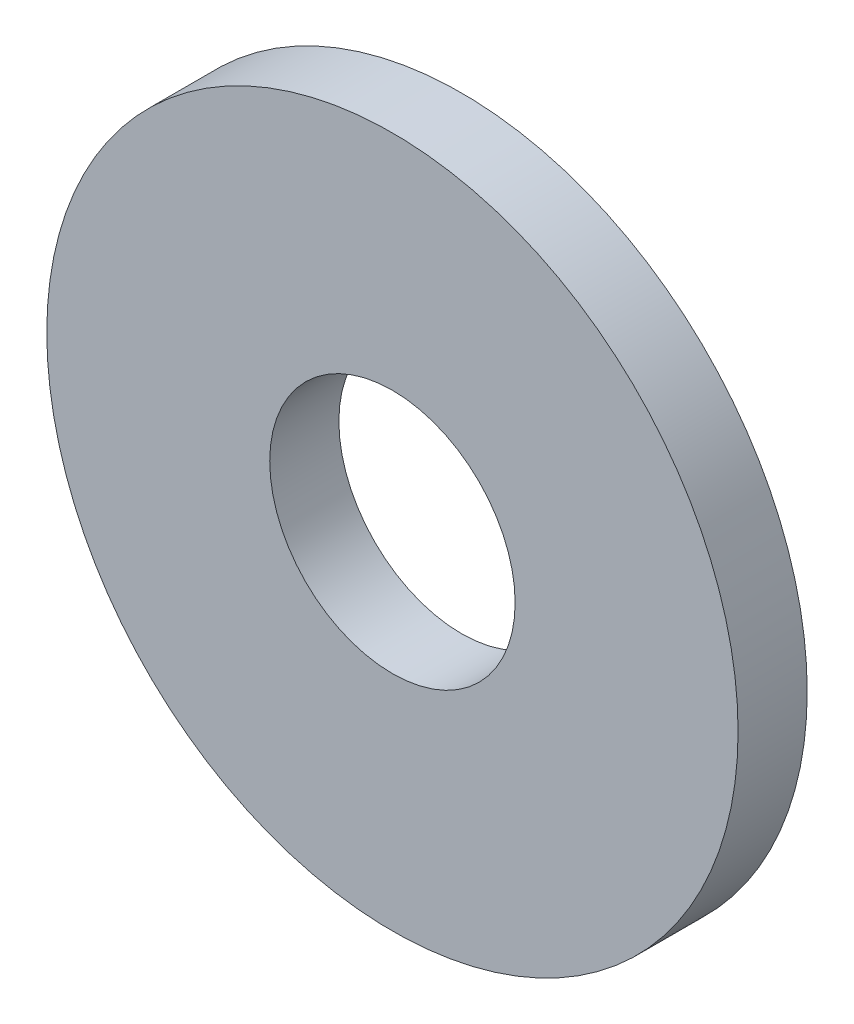
SolidWorks part; units mm, degrees
ref_plane "Ön Düzlem" through (0, 0, 0) normal (0, 0, 1) x (1, 0, 0)
ref_plane "Üst Düzlem" through (0, 0, 0) normal (0, 1, 0) x (1, 0, 0)
ref_plane "Sağ Düzlem" through (0, 0, 0) normal (1, 0, 0) x (0, 0, -1)
sketch "Çizim1" plane through (0, 0, 0) normal (0, 0, 1) x (1, 0, 0)
  circle A0 centre (2902.2415, 1052.8677) radius 200
  circle A1 centre (2902.2415, 1052.8677) radius 71
  dimension "D1" = 142
  dimension "D2" = 400
base flange "Taban-Flanş1" sketch "Çizim1" thickness 40 reverse thickness direction no parameters "D1"=4
sketch "Büküm-Çizgileri1" [suppressed] plane through (0, 0, 0) normal (0, 1, 0) x (1, 0, 0)
sketch "Sınırlandırma-Kutusu1" [suppressed] plane through (0, 0, 0) normal (0, 1, 0) x (1, 0, 0)
sheet metal parameters "Sac-Levha1" thickness 40 parameters "D1"=4
flat pattern "Düz-Çoğaltma1" [suppressed]
sketch "Büküm-Çizgileri2" plane through (0, 0, 0) normal (0, 1, 0) x (1, 0, 0)
sketch3d "Sınırlandırma-Kutusu2" [suppressed]
  line L0 (199.687, 200.3122, 0) -> (200.312, -199.687, 0) construction
  line L1 (-200.3122, 199.6872, 0) -> (-199.6872, -200.312, 0) construction
  line L2 (199.687, 200.3122, 0) -> (-200.3122, 199.6872, 0) construction
  line L3 (200.312, -199.687, 0) -> (-199.6872, -200.312, 0) construction
